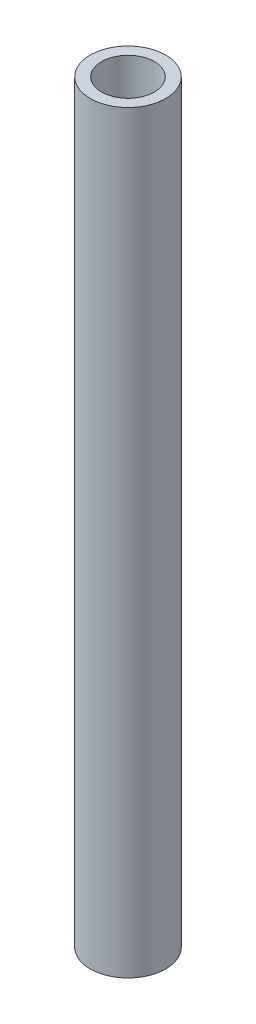
SolidWorks part; units mm, degrees
ref_plane "Front Plane" through (0, 0, 0) normal (0, 0, 1) x (1, 0, 0)
ref_plane "Top Plane" through (0, 0, 0) normal (0, 1, 0) x (1, 0, 0)
ref_plane "Right Plane" through (0, 0, 0) normal (1, 0, 0) x (0, 0, -1)
ref_axis "X" through (-88.99, 0, 0) along (1, 0, 0)
ref_axis "Y" through (0, 55, 0) along (0, -1, 0)
ref_axis "Z" through (0, 0, -88.99) along (0, 0, 1)
sketch "Sketch1" plane through (0, 0, 0) normal (0, 1, 0) x (1, 0, 0)
  circle A0 centre (0, 0) radius 5
  circle A1 centre (0, 0) radius 3.5
  point P5 (0, 0)
  point P6 (0, 0.2949)
  dimension "D1" = 10
  dimension "D2" = 7
extrude "Boss-Extrude1" add sketch "Sketch1" along normal mid plane 100
